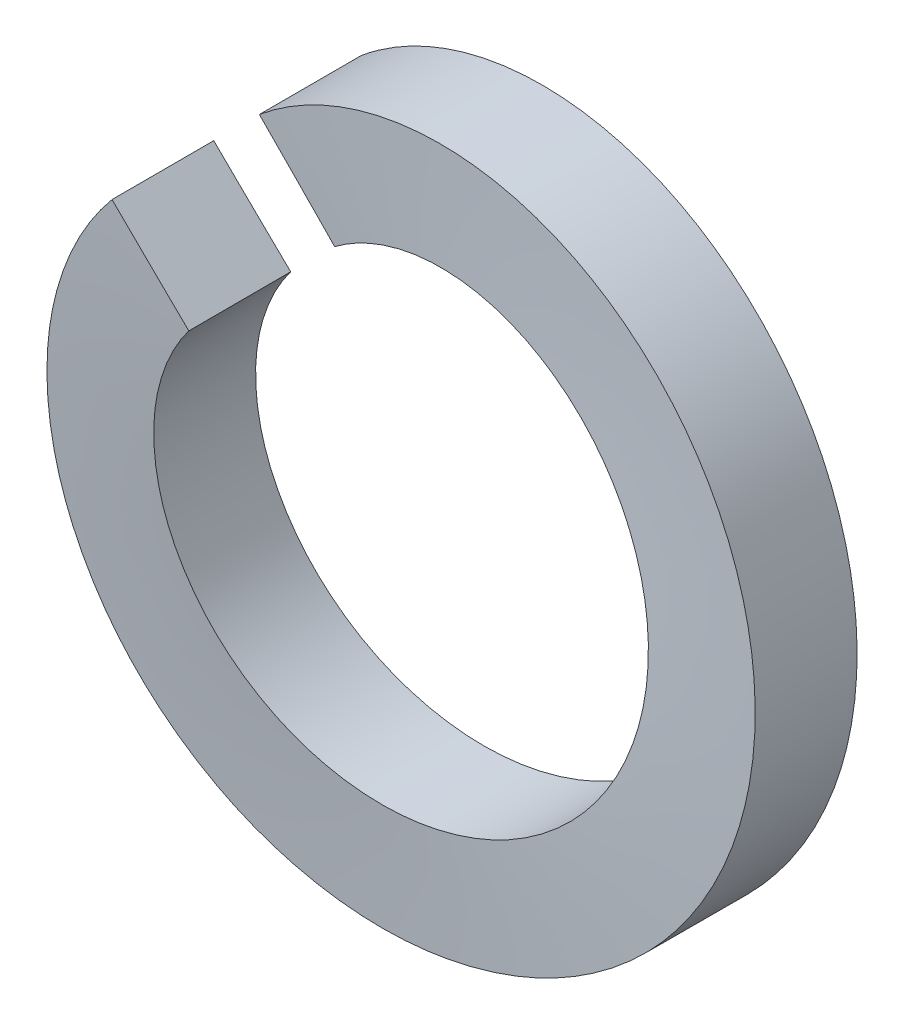
SolidWorks part; units mm, degrees
ref_plane "前视" through (0, 0, 0) normal (0, 0, 1) x (1, 0, 0)
ref_plane "上视" through (0, 0, 0) normal (0, 1, 0) x (1, 0, 0)
ref_plane "右视" through (0, 0, 0) normal (1, 0, 0) x (0, 0, -1)
sketch "尺寸草图" plane through (0, 0, 0) normal (0, 0, 1) x (1, 0, 0)
  line L0 (0, 0) -> (2.261, 0)
  point P3 (6, 0)
  point P4 (6, 0)
  point P5 (24.5, 0)
  point P6 (12, 0)
  point P7 (3, 0)
  dimension "b" = 6
  dimension "H" = 12
  dimension "d" = 24.5
  dimension "m" = 3
sketch "草图1" plane through (0, 0, 0) normal (0, 0, 1) x (1, 0, 0)
  circle A0 centre (0, 0) radius 12.25
  dimension "d" = 24.5
curve "螺旋线1" pitch 6.3 height 6.3 radius 12.25 left hand yes centre (0, 0, 0) axis (0, 0, 1) start towards (-0.7071, 0.7071, 0) parameters "h"=6.3, "p"=6.3
ref_plane "基准面2" through (-8.6621, 8.6621, 6.3) normal (0.7047, 0.7047, 0.0816) x (0.0577, 0.0577, -0.9967)
sketch "草图5" plane through (-8.6621, 8.6621, 6.3) normal (0.7047, 0.7047, 0.0816) x (0.0577, 0.0577, -0.9967)
  line L1 (0, 0) -> (5.7, 0)
  line L2 (0, 0) -> (0, 6)
  line L3 (0, 6) -> (5.7, 6)
  line L4 (5.7, 0) -> (5.7, 6)
  dimension "s" = 5.7
  dimension "b" = 6
sketch "草图6" plane through (-8.6621, 8.6621, 6.3) normal (0.7047, 0.7047, 0.0816) x (0.0577, 0.0577, -0.9967)
  line L16 (0.02, 0.02) -> (5.68, 0.02)
  line L17 (5.68, 0.02) -> (5.68, 5.98)
  line L18 (5.68, 5.98) -> (0.02, 5.98)
  line L19 (0.02, 5.98) -> (0.02, 0.02)
  line L20 (0.02, 0.02) -> (5.68, 0.02)
  line L21 (5.68, 0.02) -> (5.68, 5.98)
  line L22 (5.68, 5.98) -> (0.02, 5.98)
  line L23 (0.02, 5.98) -> (0.02, 0.02)
  dimension "D1" = 0.02
extrude "基体-拉伸" add sketch "草图6" against normal blind 0.001 and the other way blind 0.001
sketch "草图7" plane through (-8.6621, 8.6621, 6.3) normal (0.7047, 0.7047, 0.0816) x (0.0577, 0.0577, -0.9967)
  line L4 (0, 0) -> (5.7, 0)
  line L5 (5.7, 0) -> (5.7, 6)
  line L6 (5.7, 6) -> (0, 6)
  line L7 (0, 6) -> (0, 0)
  line L8 (0, 0) -> (5.7, 0)
  line L9 (5.7, 0) -> (5.7, 6)
  line L10 (5.7, 6) -> (0, 6)
  line L11 (0, 6) -> (0, 0)
  dimension "D1" = 0
sweep "凸台-扫描3" add profiles "草图7" path "螺旋线1"
sketch "草图8" plane through (-0.361, -0.361, 6.2381) normal (-0.0577, -0.0577, 0.9967) x (0.9983, -0.0037, 0.0576)
  circle A0 centre (0, 0) radius 18.2373 construction
  circle A1 centre (0, 0) radius 18.2573
  ellipse E1 centre (0, 0) end of major axis (8.6799, -8.6441) minor radius 12.2092
  ellipse E2 centre (0, 0) end of major axis (8.6799, -8.6441) minor radius 12.2092
  dimension "D1" = 0
  dimension "D2" = 0.02
extrude "凸台-拉伸1" [suppressed] add sketch "草图8" against normal blind 5.7
sketch "草图9" plane through (0, 0, 0) normal (0, 0, 1) x (1, 0, 0)
  line L0 (-34.1903, 36.3116) -> (0.8115, 1.3098)
  line L1 (-1.3098, -0.8115) -> (-38.4329, 36.3116)
  line L2 (0.8115, 1.3098) -> (-1.3098, -0.8115)
  line L3 (-34.1903, 36.3116) -> (-38.4329, 36.3116)
  line L4 (0.4223, -25.0966) -> (0.4223, -25.0114) construction
  line L6 (0, 0) -> (-2.0937, 2.0937) construction
  dimension "D1" = 3
  dimension "D2" = 49.5
  dimension "D3" = 3
  dimension "D4" = 0.3524
extrude "切除-拉伸1" cut sketch "草图9" against normal through all and the other way through all
sketch "草图10" plane through (0, 0, 0) normal (0, 0, 1) x (1, 0, 0)
  circle A0 centre (0, 0) radius 12.7792
equation "\"s@草图5\" = \"s@尺寸草图\"*0.95"
equation "\"b@草图5\" = \"b@尺寸草图\""
equation "\"d@草图1\" = \"d@尺寸草图\""
equation "\"h@螺旋线1\" = \"H@尺寸草图\" - \"s@草图5\""
equation "\"D1@凸台-拉伸1\" = \"s@草图5\""
equation "\"D1@草图9\" = \"m@尺寸草图\""
equation "\"D3@草图9\" = \"m@尺寸草图\""
